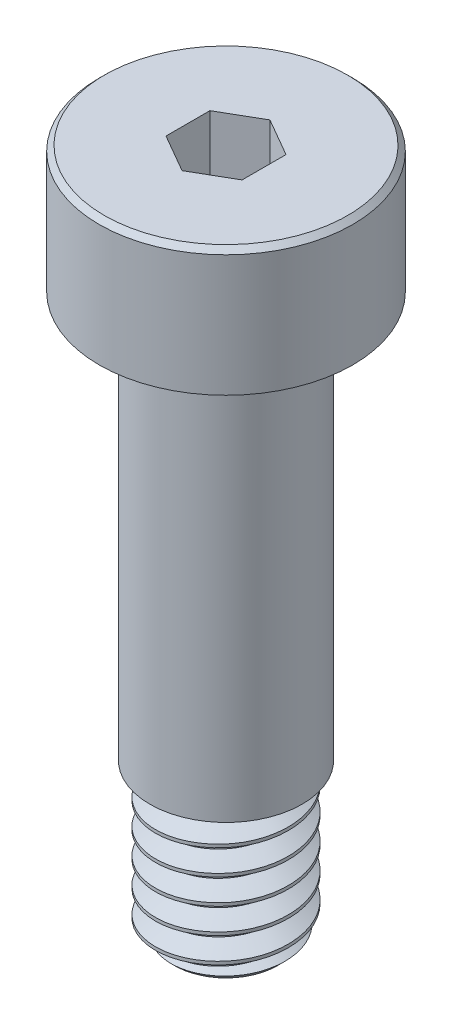
SolidWorks part; units mm, degrees
material "Alloy Steel (SS)"
ref_plane "Front" through (0, 0, 0) normal (0, 0, 1) x (1, 0, 0)
ref_plane "Top" through (0, 0, 0) normal (0, 1, 0) x (1, 0, 0)
ref_plane "Right" through (0, 0, 0) normal (1, 0, 0) x (0, 0, -1)
sketch "Sketch1" plane through (0, 0, 0) normal (0, 1, 0) x (1, 0, 0)
  circle A0 centre (0, 0) radius 3.9688
  point P3 (0, -3.9688)
  dimension "Head Dia" = 7.9375
extrude "Extrude1" add sketch "Sketch1" along normal blind 3.9688
sketch "Sketch2" plane through (0, 3.9688, 0) normal (0, 1, 0) x (-1, 0, 0)
  line L1 (0, -1.3748) -> (1.1906, -0.6874)
  line L2 (1.1906, -0.6874) -> (1.1906, 0.6874)
  line L3 (1.1906, 0.6874) -> (0, 1.3748)
  line L4 (0, 1.3748) -> (-1.1906, 0.6874)
  line L5 (-1.1906, 0.6874) -> (-1.1906, -0.6874)
  line L6 (-1.1906, -0.6874) -> (0, -1.3748)
  circle A0 centre (0, 0) radius 1.1906 construction
  circle A1 centre (0, 0) radius 3.9688 construction
  dimension "Hex Key" = 2.3813
extrude "Cut-Extrude1" cut sketch "Sketch2" against normal blind 1.9844
sketch "Sketch4" plane through (0, 0, 0) normal (0, -1, 0) x (1, 0, 0)
  circle A0 centre (0, 0) radius 2.3813
  circle A1 centre (0, 0) radius 3.9688 construction
  dimension "Shoulder Dia" = 4.7625
extrude "Extrude2" add sketch "Sketch4" along normal blind 12.7
sketch "Sketch5" plane through (0, -12.7, 0) normal (0, -1, 0) x (1, 0, 0)
  circle A0 centre (0, 0) radius 2.0828
  circle A1 centre (0, 0) radius 2.3813 construction
  dimension "Thread Dia" = 4.1656
extrude "Extrude3" add sketch "Sketch5" along normal blind 4.7625
chamfer "Chamfer1" distance 0.4763 angle 45 1 edges at (0, -17.4625, -2.0828)
sketch "Sketch12" plane through (0, -17.4625, 0) normal (0, -1, 0) x (1, 0, 0)
  circle A0 centre (0, 0) radius 2.0828
  circle A1 centre (0, 0) radius 2.0828 construction
curve "Helix/Spiral1" pitch 0.7937 height 4.7625 turns 6 parameters "Thread Pitch "=0.7937
sketch "Sketch13" plane through (0, 0, 0) normal (0, 0, 1) x (1, 0, 0)
  line L0 (2.0828, -17.4625) -> (2.0828, -18.157)
  line L1 (2.0828, -18.157) -> (1.5672, -17.8594)
  line L2 (1.5672, -17.8594) -> (1.5672, -17.7602)
  line L3 (1.5672, -17.7602) -> (2.0828, -17.4625)
  line L4 (2.0828, -17.8098) -> (1.5672, -17.8098) construction
  line L5 (2.0828, -16.9863) -> (2.0828, -12.7) construction
  line L6 (1.825, -17.6113) -> (1.825, -18.0082) construction
  line L7 (-1.6066, -17.4625) -> (1.6066, -17.4625) construction
  dimension "D1" = 60
  dimension "D2" = 0.0992
  dimension "D3" = 0.3969
sweep "Cut-Sweep1" cut profiles "Sketch13" path "Helix/Spiral1"
sketch "Sketch10" plane through (0, 3.9688, 0) normal (0, 1, 0) x (-1, 0, 0)
  line L0 (0, 0) -> (-3.8069, 0) construction
  line L1 (0, 0) -> (-11.9081, -0.5199) construction
  line L2 (-3.965, -0.1731) -> (-4.0231, -0.1757)
  line L3 (-3.965, -0.1731) -> (-3.8175, -0.0257)
  line L4 (0, 0) -> (-11.9081, 0.5199) construction
  line L5 (-3.8175, 0.0257) -> (-3.965, 0.1731)
  line L6 (-4.0231, -0.1757) -> (-4.0231, 0.1757)
  line L7 (-4.0231, 0.1757) -> (-3.965, 0.1731)
  circle A0 centre (0, 0) radius 3.9688 construction
  arc A2 (-3.8175, -0.0257) -> (-3.8175, 0.0257) centre (-3.8432, 0) ccw
  point P3 (-3.9688, 0)
  dimension "D4" = 0.0363
  dimension "D1" = 90
  dimension "D2" = 5
  dimension "D3" = 0.0581
sketch "Sketch11" plane through (0, 0, 0) normal (0, 0, 1) x (1, 0, 0)
  line L0 (3.9688, 3.8069) -> (3.8069, 3.9688)
  line L1 (3.8069, 3.9688) -> (3.9688, 3.9688)
  line L2 (3.9688, 3.9688) -> (3.9688, 3.8069)
  line L3 (3.8175, 3.9688) -> (3.8069, 3.9688) construction
  line L6 (0, 14.5442) -> (0, -6.8202) construction
revolve "Cut-Revolve7" cut sketch "Sketch11" angle 360 about L6
sketch "Sketch14" plane through (0, 3.9688, 0) normal (0, 1, 0) x (1, 0, 0)
  circle A0 centre (0, 0) radius 3.9688
  circle A2 centre (0, 0) radius 3.9688 construction
sketch "Sketch15" plane through (0, 0, 0) normal (1, 0, 0) x (0, 0, -1)
  line L0 (-2.0828, -12.7) -> (-2.0828, -17.4625) construction
  line L1 (2.0828, -17.4625) -> (2.0828, -12.7) construction
  line L2 (-2.3813, -12.7) -> (2.3813, -12.7) construction
equation "\"D1@Cut-Extrude1\"=\"Head Ht@Extrude1\"/2"
equation "\"D1@Chamfer1\" = \"Thread Length@Extrude3\" * .1"
equation "\"D3@Helix/Spiral1\" = \"Thread Length@Extrude3\""
equation "\"D2@Sketch13\" = \"Thread Pitch @Helix/Spiral1\" * .125"
equation "\"D3@Sketch13\" = \"Thread Pitch @Helix/Spiral1\" * .5"
equation "\"D3@Sketch10\" = \"Head Dia@Sketch1\" * .0073205143"
equation "\"D4@Sketch10\" = \"Head Dia@Sketch1\" * .0045714286"
